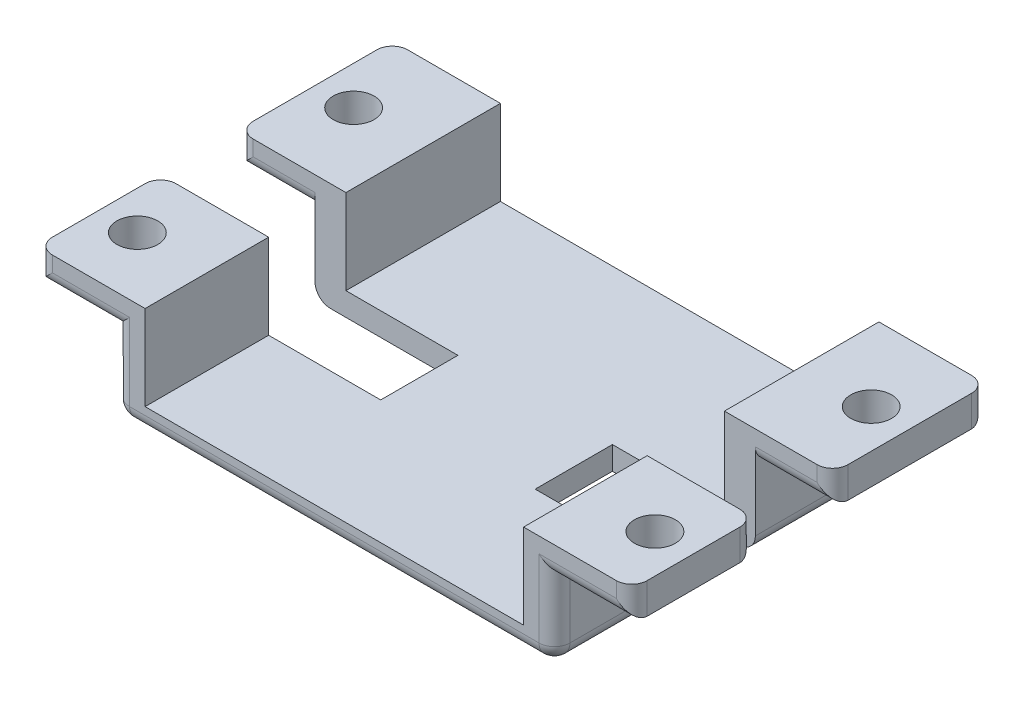
SolidWorks part; units mm, degrees
ref_plane "Front Plane" through (0, 0, 0) normal (0, 0, 1) x (1, 0, 0)
ref_plane "Top Plane" through (0, 0, 0) normal (0, 1, 0) x (1, 0, 0)
ref_plane "Right Plane" through (0, 0, 0) normal (1, 0, 0) x (0, 0, -1)
sketch "Sketch1" plane through (0, 0, 0) normal (0, 0, 1) x (1, 0, 0)
  line L1 (-12.25, -16.5) -> (12.25, -16.5)
  line L2 (-12.25, -16.5) -> (-12.25, 16.5)
  line L3 (-12.25, 16.5) -> (12.25, 16.5)
  line L4 (12.25, -16.5) -> (12.25, 16.5)
  line L5 (-12.25, -16.5) -> (12.25, 16.5) construction
  line L6 (-12.25, 16.5) -> (12.25, -16.5) construction
  line L7 (-14.25, -18) -> (14.25, -18)
  line L8 (-14.25, -18) -> (-14.25, 18)
  line L9 (-14.25, 18) -> (14.25, 18)
  line L10 (14.25, -18) -> (14.25, 18)
  line L11 (-14.25, -18) -> (14.25, 18) construction
  line L12 (-14.25, 18) -> (14.25, -18) construction
  point P0 (0, 0)
  point P6 (0, 0)
  dimension "D1" = 24.5
  dimension "D2" = 33
  dimension "D3" = 1.5
  dimension "D4" = 2
extrude "Boss-Extrude1" add sketch "Sketch1" along normal blind 10
sketch "Sketch2" plane through (0, 0, 10) normal (0, 0, 1) x (1, 0, 0)
  line L0 (0, -16.5) -> (0, 16.5) construction
  line L1 (-12.25, -16.5) -> (12.25, -16.5) construction
  line L2 (12.25, 16.5) -> (-12.25, 16.5) construction
  line L3 (-14.25, 18) -> (-14.25, -18) construction
  line L4 (-19.25, -13) -> (19.25, -13)
  line L5 (-19.25, -13) -> (-19.25, -9)
  line L6 (-19.25, -9) -> (19.25, -9)
  line L7 (19.25, -13) -> (19.25, -9)
  line L8 (-19.25, -13) -> (19.25, -9) construction
  line L9 (-19.25, -9) -> (19.25, -13) construction
  line L10 (-14.25, -18) -> (14.25, -18) construction
  line L11 (-14.25, 18) -> (-14.25, -18)
  line L12 (14.25, -18) -> (14.25, 18) construction
  line L13 (14.25, -18) -> (14.25, 18)
  point P6 (0, -11)
  line M3 (14.25, -18) -> (14.25, 18)
  line M5 (-14.25, 18) -> (-14.25, -18)
  dimension "D1" = 5
  dimension "D2" = 4
  dimension "D3" = 5
extrude "Boss-Extrude2" add sketch "Sketch2" against normal up to surface (10 mm away) contours L6 L5 L4 M5 | L4 L7 L6 M3 up to face at (0, 0, 0)
ref_plane "Plane1" through (0, -11, 0) normal (0, -1, 0) x (-1, 0, 0)
sketch "Sketch3" plane through (0, -9, 0) normal (0, 1, 0) x (1, 0, 0)
  line L0 (14.25, -5) -> (19.25, -5) construction
  line L1 (14.25, -10) -> (14.25, 0) construction
  line L2 (19.25, 0) -> (19.25, -10) construction
  line L3 (-19.25, -5) -> (-14.25, -5) construction
  line L4 (-19.25, 0) -> (-19.25, -10) construction
  line L5 (-14.25, -10) -> (-14.25, 0) construction
  circle A0 centre (-16.75, -5) radius 1.325
  circle A1 centre (16.75, -5) radius 1.325
  dimension "D1" = 2.65
  dimension "D2" = 2.65
extrude "Cut-Extrude1" cut sketch "Sketch3" against normal blind 10
split "Split1" trim tools "Plane1" bodies to split 103 resulting bodies 104 105
fillet "Fillet1" radius 1 11 edges at (0, 18, 0) (-19.25, -10, 0) (-14.25, 4.5, 0) (-16.75, -9, 0) (-19.25, -10, 10) (-16.75, -9, 10) (14.25, 4.5, 0) (16.75, -9, 0) (19.25, -10, 0) (19.25, -10, 10) (16.75, -9, 10)
fillet "Fillet2" radius 1 11 edges at (-16.75, -13, 0) (-16.75, -13, 10) (16.75, -13, 0) (16.75, -13, 10) (19.25, -12, 10) (19.25, -12, 0) (0, -18, 0) (14.25, -15.5, 0) (-14.25, -15.5, 0) (-19.25, -12, 0) (-19.25, -12, 10)
sketch "Sketch4" plane through (-14.25, 0, 0) normal (-1, 0, 0) x (0, 0, 1)
  line L0 (5, 18) -> (5, -9) construction
  line L2 (1, -9) -> (9, -9) construction
  line L3 (5, 12.5) -> (5, -3.5) construction
  line L4 (7, 12.5) -> (7, -3.5)
  line L5 (3, 12.5) -> (3, -3.5)
  line L6 (10, 18) -> (1, 18) construction
  arc A0 (7, 12.5) -> (3, 12.5) centre (5, 12.5) ccw
  arc A1 (3, -3.5) -> (7, -3.5) centre (5, -3.5) ccw
  point P2 (5, 18)
  point P8 (5, 4.5)
  dimension "D2" = 20
  dimension "D1" = 4
extrude "Cut-Extrude2" cut sketch "Sketch4" against normal through all
delete or keep bodies "Body-Delete/Keep 1" [suppressed] type keep bodies bodies 104
sketch "Sketch5" plane through (0, 0, 10) normal (0, 0, 1) x (1, 0, 0)
  line L0 (0, 18) -> (0, 16.5) construction
  line L1 (14.25, 18) -> (-14.25, 18) construction
  line L2 (12.25, 16.5) -> (-12.25, 16.5) construction
  line L3 (-14.25, 4) -> (-12.25, 4) construction
  line L4 (-14.25, 18) -> (-14.25, -10) construction
  line L5 (-12.25, 16.5) -> (-12.25, -11) construction
  line L6 (12.25, 4) -> (14.25, 4) construction
  line L7 (12.25, -11) -> (12.25, 16.5) construction
  line L8 (14.25, -10) -> (14.25, 18) construction
  line L10 (-7.5, 18) -> (7.5, 18)
  line L11 (-7.5, 18) -> (-7.5, 16.5)
  line L12 (-7.5, 16.5) -> (7.5, 16.5)
  line L13 (7.5, 18) -> (7.5, 16.5)
  line L14 (-7.5, 18) -> (7.5, 16.5) construction
  line L15 (-7.5, 16.5) -> (7.5, 18) construction
  line L16 (-14.25, -1) -> (-12.25, -1)
  line L17 (-14.25, -1) -> (-14.25, 9)
  line L18 (-14.25, 9) -> (-12.25, 9)
  line L19 (-12.25, -1) -> (-12.25, 9)
  line L20 (-14.25, -1) -> (-12.25, 9) construction
  line L21 (-14.25, 9) -> (-12.25, -1) construction
  line L22 (12.25, -1) -> (14.25, -1)
  line L23 (12.25, -1) -> (12.25, 9)
  line L24 (12.25, 9) -> (14.25, 9)
  line L25 (14.25, -1) -> (14.25, 9)
  line L26 (12.25, -1) -> (14.25, 9) construction
  line L27 (12.25, 9) -> (14.25, -1) construction
  point P18 (0, 17.25)
  point P23 (-13.25, 4)
  point P28 (13.25, 4)
  dimension "D1" = 15
  dimension "D2" = 10
extrude "Boss-Extrude3" add sketch "Sketch5" along normal blind 5
sketch "Sketch6" plane through (0, 0, 10) normal (0, 0, 1) x (1, 0, 0)
  line L0 (0, -18) -> (0, -16.5) construction
  line L1 (-14.25, -18) -> (14.25, -18) construction
  line L2 (-12.25, -16.5) -> (12.25, -16.5) construction
  line L4 (-5, -18) -> (5, -18)
  line L5 (-5, -18) -> (-5, -16.5)
  line L6 (-5, -16.5) -> (5, -16.5)
  line L7 (5, -18) -> (5, -16.5)
  line L8 (-5, -18) -> (5, -16.5) construction
  line L9 (-5, -16.5) -> (5, -18) construction
  point P6 (0, -17.25)
  dimension "D1" = 10
extrude "Boss-Extrude4" add sketch "Sketch6" along normal blind 5
sketch "Sketch7" plane through (0, 0, 15) normal (0, 0, 1) x (1, 0, 0)
  line L0 (14.25, 9) -> (14.25, 18) construction
  line L1 (14.25, -1) -> (14.25, 9) construction
  line L2 (14.25, -10) -> (14.25, -1) construction
  line L3 (12.25, -11) -> (12.25, -1) construction
  line L4 (12.25, 9) -> (12.25, -1) construction
  line L5 (12.25, 9) -> (12.25, 16.5) construction
  line L6 (12.25, 16.5) -> (7.5, 16.5) construction
  line L7 (-7.5, 16.5) -> (7.5, 16.5) construction
  line L8 (-7.5, 16.5) -> (-12.25, 16.5) construction
  line L9 (-14.25, 18) -> (-14.25, 9) construction
  line L10 (-14.25, 9) -> (-14.25, -1) construction
  line L11 (-14.25, -1) -> (-14.25, -10) construction
  line L12 (-12.25, -1) -> (-12.25, -11) construction
  line L13 (-12.25, -1) -> (-12.25, 9) construction
  line L14 (-12.25, 16.5) -> (-12.25, 9) construction
  line L15 (14.25, 9) -> (14.25, 18)
  line L16 (14.25, -1) -> (14.25, 9)
  line L17 (14.25, -10) -> (14.25, -1)
  line L18 (12.25, -11) -> (12.25, -1)
  line L19 (12.25, 9) -> (12.25, -1)
  line L20 (12.25, 9) -> (12.25, 16.5)
  line L21 (12.25, 16.5) -> (7.5, 16.5)
  line L22 (-7.5, 16.5) -> (7.5, 16.5)
  line L23 (-7.5, 16.5) -> (-12.25, 16.5)
  line L24 (-14.25, 18) -> (-14.25, 9)
  line L25 (-14.25, 9) -> (-14.25, -1)
  line L26 (-14.25, -1) -> (-14.25, -10)
  line L27 (-12.25, -1) -> (-12.25, -11)
  line L28 (-12.25, -1) -> (-12.25, 9)
  line L29 (-12.25, 16.5) -> (-12.25, 9)
  line L30 (-14.25, -10) -> (-14.25, -11)
  line L31 (-7.7, -11) -> (7.7, -11) construction
  line L32 (-14.25, -11) -> (-12.25, -11)
  line L33 (-14.25, 18) -> (-14.25, 19.5)
  line L34 (-14.25, 19.5) -> (14.25, 19.5)
  line L35 (14.25, 19.5) -> (14.25, 18)
  line L36 (14.25, -10) -> (14.25, -11)
  line L37 (14.25, -11) -> (12.25, -11)
  line L38 (7.5, 18) -> (-7.5, 18) construction
  dimension "D1" = 1.5
extrude "Boss-Extrude5" add sketch "Sketch7" along normal blind 8
sketch "Sketch8" plane through (0, 0, 23) normal (0, 0, 1) x (1, 0, 0)
  line L0 (-12.25, 16.5) -> (12.25, 16.5) construction
  line L1 (-3.5, 15) -> (3.5, 15)
  line L2 (-3.5, 15) -> (-3.5, 18)
  line L3 (-3.5, 18) -> (3.5, 18)
  line L4 (3.5, 15) -> (3.5, 18)
  line L5 (-3.5, 15) -> (3.5, 18) construction
  line L6 (-3.5, 18) -> (3.5, 15) construction
  point P0 (0, 16.5)
  dimension "D1" = 1.5
  dimension "D2" = 7
extrude "Cut-Extrude3" cut sketch "Sketch8" against normal offset from surface (5 mm away) 3 up to face at (0, 14.75, 15)
sketch "Sketch9" plane through (0, 0, 23) normal (0, 0, 1) x (1, 0, 0)
  line L0 (-3.5, 16.5) -> (3.5, 16.5) construction
  line L1 (3.5, 16.5) -> (8.5, 16.5)
  line L2 (3.5, 16.5) -> (3.5, 18.6)
  line L3 (3.5, 18.6) -> (8.5, 18.6)
  line L4 (8.5, 16.5) -> (8.5, 18.6)
  line L5 (-3.5, 16.5) -> (-8.5, 16.5)
  line L6 (-3.5, 16.5) -> (-3.5, 18.6)
  line L7 (-3.5, 18.6) -> (-8.5, 18.6)
  line L8 (-8.5, 16.5) -> (-8.5, 18.6)
  dimension "D1" = 5
  dimension "D2" = 2.1
extrude "Cut-Extrude4" cut sketch "Sketch9" against normal up to surface (5 mm away) up to face at (0, 17.25, 18)
sketch "Sketch10" plane through (0, 0, 15) normal (0, 0, 1) x (1, 0, 0)
  line L0 (12.25, -16.5) -> (12.25, -1) construction
  line L1 (-12.25, -1) -> (-12.25, -16.5) construction
  line L2 (-12.25, -16.5) -> (-5, -16.5) construction
  line L3 (5, -16.5) -> (-5, -16.5) construction
  line L4 (5, -16.5) -> (12.25, -16.5) construction
  line L5 (14.25, -18) -> (14.25, -12) construction
  line L6 (5, -18) -> (14.25, -18) construction
  line L7 (-5, -18) -> (5, -18) construction
  line L8 (-14.25, -12) -> (-14.25, -18) construction
  line L9 (-14.25, -18) -> (-5, -18) construction
  line L10 (12.25, -16.5) -> (12.25, -1)
  line L11 (-12.25, -1) -> (-12.25, -16.5)
  line L12 (-12.25, -16.5) -> (-5, -16.5)
  line L13 (5, -16.5) -> (-5, -16.5)
  line L14 (5, -16.5) -> (12.25, -16.5)
  line L15 (14.25, -18) -> (14.25, -12)
  line L16 (5, -18) -> (14.25, -18)
  line L17 (-5, -18) -> (5, -18)
  line L18 (-14.25, -12) -> (-14.25, -18)
  line L19 (-14.25, -18) -> (-5, -18)
  line L20 (-14.25, -12) -> (-14.25, -11)
  line L21 (-7.7, -11) -> (7.7, -11) construction
  line L22 (-14.25, -11) -> (-12.25, -11)
  line L23 (14.25, -12) -> (14.25, -11)
  line L24 (14.25, -11) -> (12.25, -11)
  line M1 (5, -18) -> (5, -16.5)
  line M2 (5, -16.5) -> (-5, -16.5)
  line M3 (-5, -16.5) -> (-5, -18)
  line M4 (-5, -18) -> (5, -18)
extrude "Boss-Extrude6" add sketch "Sketch10" along normal up to surface (8 mm away) contours L22 L20 L18 L19 L12 L11 M3 | M4 M1 M2 M3 | L23 L24 L10 L14 L16 L15 M1 up to face at (0, 10.7125, 23)
sketch "Sketch11" plane through (0, 0, 23) normal (0, 0, 1) x (1, 0, 0)
  line L0 (-14.25, -13) -> (-19.25, -13) construction
  line L1 (-19.25, -9) -> (-14.25, -9) construction
  line L2 (-19.25, -13) -> (-19.25, -9) construction
  line L3 (-14.25, -13) -> (-19.25, -13)
  line L4 (-19.25, -9) -> (-14.25, -9)
  line L5 (-19.25, -13) -> (-19.25, -9)
  line L6 (19.25, -13) -> (14.25, -13) construction
  line L7 (19.25, -9) -> (19.25, -13) construction
  line L8 (14.25, -9) -> (19.25, -9) construction
  line L9 (19.25, -13) -> (14.25, -13)
  line L10 (19.25, -9) -> (19.25, -13)
  line L11 (14.25, -9) -> (19.25, -9)
  line L12 (-14.25, -9) -> (-14.25, -13)
  line L13 (14.25, -9) -> (14.25, -13)
extrude "Boss-Extrude7" add sketch "Sketch11" against normal up to surface (8 mm away) up to face at (0, 14.75, 15)
sketch "Sketch12" plane through (0, -9, 0) normal (0, 1, 0) x (1, 0, 0)
  line L0 (-16.75, -5) -> (-16.75, -15) construction
  line L1 (-14.25, -15) -> (-19.25, -15) construction
  line L2 (-16.75, -15) -> (-16.75, -23) construction
  line L3 (-14.25, -23) -> (-19.25, -23) construction
  line L4 (16.75, -5) -> (16.75, -10) construction
  line L5 (18.25, -10) -> (14.25, -10) construction
  line L6 (16.75, -10) -> (16.75, -15) construction
  line L7 (19.25, -15) -> (14.25, -15) construction
  line L8 (16.75, -15) -> (16.75, -23) construction
  line L9 (19.25, -23) -> (14.25, -23) construction
  circle A0 centre (-16.75, -19) radius 1.325
  circle A1 centre (16.75, -19) radius 1.325
  circle A2 centre (-16.75, -5) radius 1.325 construction
extrude "Cut-Extrude5" cut sketch "Sketch12" against normal through all
sketch "Sketch13" plane through (-14.25, 0, 0) normal (-1, 0, 0) x (0, 0, 1)
  line L0 (3, 4.5) -> (23, 4.5) construction
  line L1 (3, 12.5) -> (3, -3.5) construction
  line L2 (23, 19.5) -> (23, -9) construction
  line L3 (19, 19.5) -> (19, 4.5) construction
  line L4 (23, 19.5) -> (15, 19.5) construction
  line L5 (19, -3.5) -> (19, 12.5) construction
  line L6 (17, -3.5) -> (17, 12.5)
  line L7 (21, -3.5) -> (21, 12.5)
  line L8 (7, -3.5) -> (7, 12.5) construction
  arc A0 (17, -3.5) -> (21, -3.5) centre (19, -3.5) ccw
  arc A1 (21, 12.5) -> (17, 12.5) centre (19, 12.5) ccw
  arc A2 (7, 12.5) -> (3, 12.5) centre (5, 12.5) ccw construction
  point P12 (19, 4.5)
extrude "Cut-Extrude6" cut sketch "Sketch13" against normal through all
fillet "Fillet3" radius 1 29 edges at (-14.25, 18, 5.5) (14.25, 18, 5.5) (14.25, 19.5, 19) (-14.25, 19.5, 19) (14.25, -15.5, 23) (-14.25, 5.25, 23) (-14.25, -18, 5.5) (14.25, -18, 5.5) (13.9571, -17.7071, 0.2929) (-13.9571, -17.7071, 0.2929) (0, -18, 23) (-14.25, -18, 19) (14.25, -18, 19) (-14.25, -15.5, 23) (-16.75, -9, 23) (-19.25, -11, 23) (-16.75, -13, 23) (-16.75, -9, 15) (-19.25, -11, 15) (-16.75, -13, 15) (14.25, 5.25, 23) (19.25, -11, 23) (16.75, -9, 23) (16.75, -13, 23) (16.75, -9, 15) (16.75, -13, 15) (19.25, -11, 15) (13.9571, 17.7071, 0.2929) (-13.9571, 17.7071, 0.2929)
split "Split2" trim tools "Plane1" bodies to split 115 resulting bodies 116 117
delete or keep bodies "Body-Delete/Keep 2" type keep bodies bodies 116
